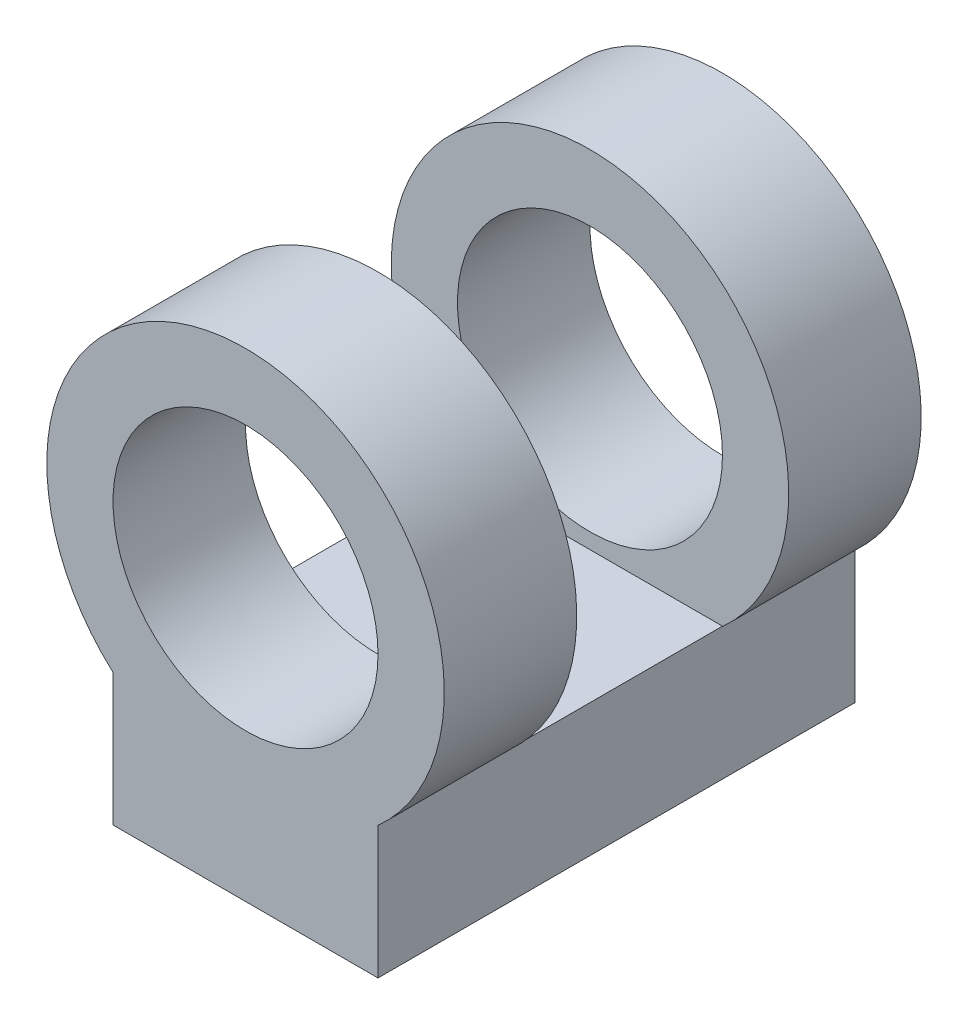
SolidWorks part; units mm, degrees
ref_plane "Front Plane" through (0, 0, 0) normal (0, 0, 1) x (1, 0, 0)
ref_plane "Top Plane" through (0, 0, 0) normal (0, 1, 0) x (1, 0, 0)
ref_plane "Right Plane" through (0, 0, 0) normal (1, 0, 0) x (0, 0, -1)
sketch "Sketch1" plane through (0, 0, 0) normal (0, 1, 0) x (1, 0, 0)
  line L1 (-25, 45) -> (25, 45)
  line L2 (-25, 45) -> (-25, -45)
  line L3 (-25, -45) -> (25, -45)
  line L4 (25, 45) -> (25, -45)
  line L5 (-25, 45) -> (25, -45) construction
  line L6 (-25, -45) -> (25, 45) construction
  point P0 (0, 0)
  dimension "D1" = 50
  dimension "D2" = 90
extrude "Boss-Extrude1" add sketch "Sketch1" along normal blind 25 contours L3 L4 L1 L2
ref_plane "Plane1" through (0, 0, 45) normal (0, 0, 1) x (1, 0, 0)
sketch "Sketch2" plane through (0, 0, 45) normal (0, 0, 1) x (1, 0, 0)
  line L0 (0, 0) -> (0, 52.9) construction
  line L1 (-25, 25) -> (25, 25) construction
  circle A0 centre (0, 52.9) radius 37.5
  dimension "D2" = 75
  dimension "D1" = 27.9
extrude "Boss-Extrude2" add sketch "Sketch2" against normal blind 25 contours A0
sketch "Sketch3" plane through (0, 0, 45) normal (0, 0, 1) x (1, 0, 0)
  circle A0 centre (0, 52.9) radius 25
extrude "Cut-Extrude1" cut sketch "Sketch3" against normal blind 25
pattern_linear "LPattern3" count 2 spacing 65 along (0, 0, -1) of "Boss-Extrude2", "Cut-Extrude1"
ref_axis "Axis1" through (0, -4.52, 0) along (0, 1, 0)
ref_axis "Axis2" through (0, 52.9, 20) along (0, 0, 1)
ref_axis "Axis3" through (0, 52.9, -45) along (0, 0, 1)
